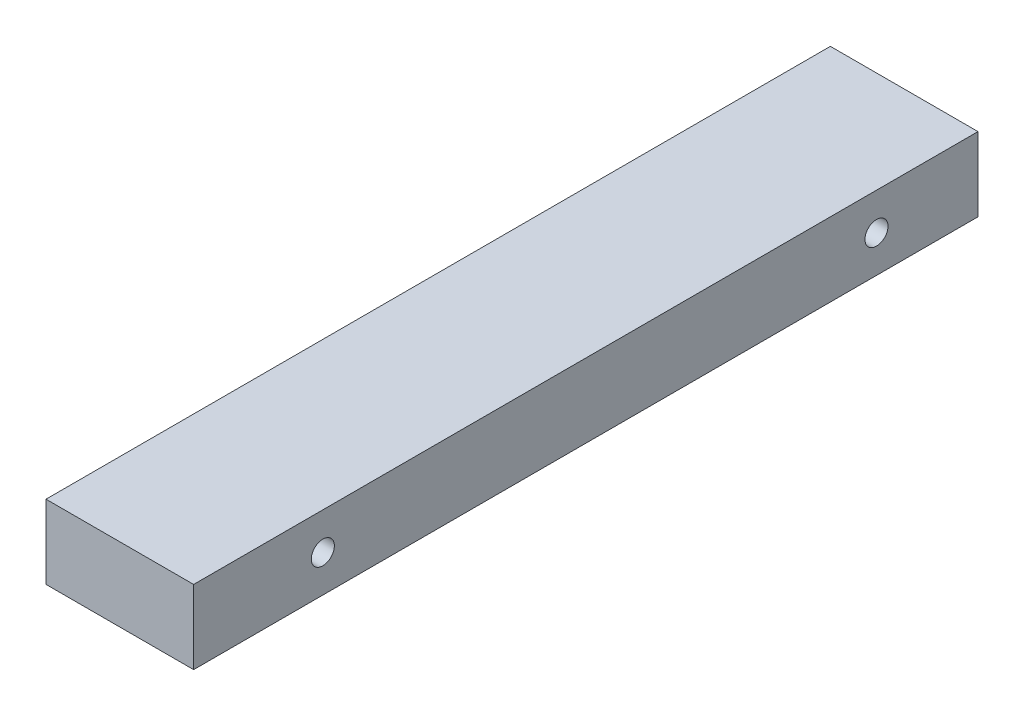
SolidWorks part; units mm, degrees
ref_plane "Front Plane" through (0, 0, 0) normal (0, 0, 1) x (1, 0, 0)
ref_plane "Top Plane" through (0, 0, 0) normal (0, 1, 0) x (1, 0, 0)
ref_plane "Right Plane" through (0, 0, 0) normal (1, 0, 0) x (0, 0, -1)
sketch "Sketch1" plane through (0, 0, 0) normal (0, 0, 1) x (1, 0, 0)
  line L1 (0, 0) -> (-101.6, 0)
  line L2 (0, 0) -> (0, 50.8)
  line L3 (0, 50.8) -> (-101.6, 50.8)
  line L4 (-101.6, 0) -> (-101.6, 50.8)
  dimension "D1" = 50.8
  dimension "D2" = 101.6
extrude "Boss-Extrude1" add sketch "Sketch1" along normal blind 539.75
sketch "Sketch2" plane through (-101.6, 0, 0) normal (-1, 0, 0) x (0, 0, 1)
  line L0 (539.75, 0) -> (0, 0) construction
  circle A0 centre (69.85, 25.4) radius 7.9375
  circle A1 centre (450.85, 25.4) radius 7.9375
  dimension "D1" = 25.4
  dimension "D2" = 25.4
  dimension "D3" = 381
extrude "Cut-Extrude1" cut sketch "Sketch2" against normal blind 539.75
